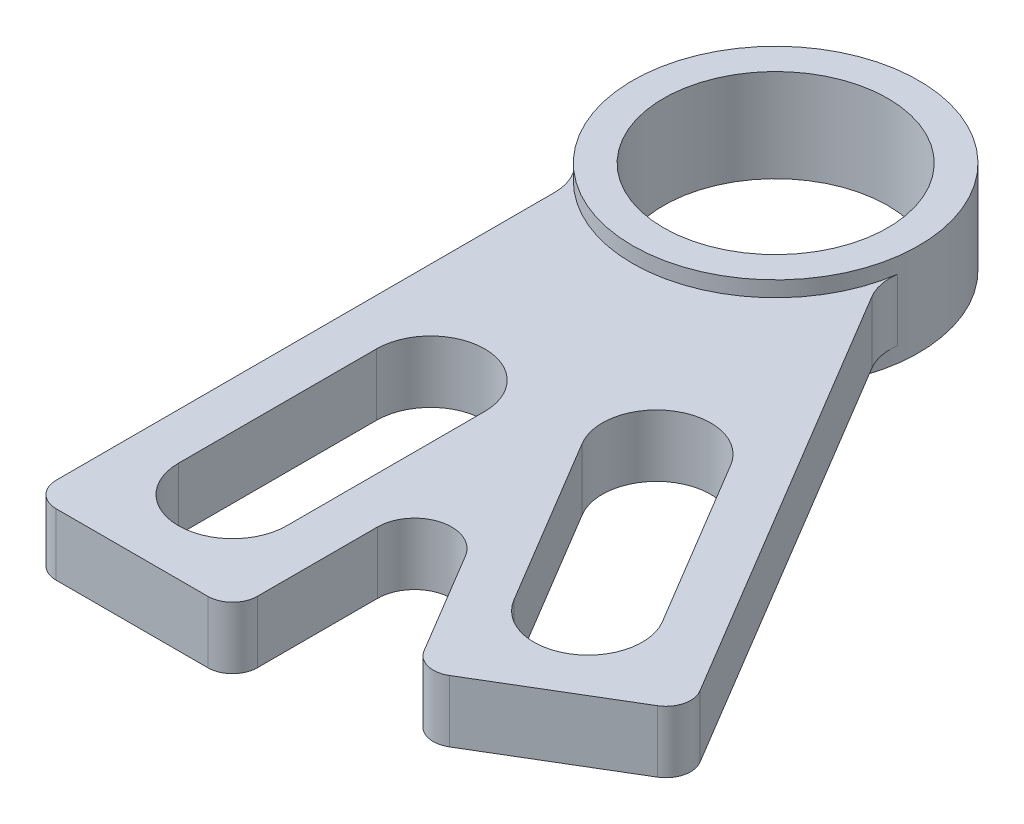
SolidWorks part; units mm, degrees
material "AISI 4130 Steel, normalized at 870C"
ref_plane "Front Plane" through (0, 0, 0) normal (0, 0, 1) x (1, 0, 0)
ref_plane "Top Plane" through (0, 0, 0) normal (0, 1, 0) x (1, 0, 0)
ref_plane "Right Plane" through (0, 0, 0) normal (1, 0, 0) x (0, 0, -1)
sketch "Sketch1" plane through (0, 0, 0) normal (0, 1, 0) x (1, 0, 0)
  line L0 (0, 0) -> (0, -66.04) construction
  line L1 (0, 0) -> (33.8815, -56.6862) construction
  line L2 (0, -55.7213) -> (0, -35.4013) construction
  line L3 (-5.5562, -55.7213) -> (-5.5562, -35.4013)
  line L4 (5.5563, -55.7213) -> (5.5563, -35.4013)
  line L5 (28.5875, -47.829) -> (18.1624, -30.3871) construction
  line L6 (23.8182, -50.6796) -> (13.3931, -33.2377)
  line L7 (33.3568, -44.9784) -> (22.9317, -27.5365)
  line L8 (0, -66.04) -> (0, -61.2775) construction
  line L9 (33.8815, -56.6862) -> (31.4381, -52.5983) construction
  line L10 (-10.3187, -66.04) -> (10.3188, -66.04)
  line L11 (25.0242, -61.9802) -> (42.7387, -51.3923)
  line L12 (-10.3187, -66.04) -> (-10.3187, -10.4432)
  line L13 (10.3188, -66.04) -> (10.3188, -37.3768)
  line L14 (42.7387, -51.3923) -> (14.2151, -3.6701)
  line L15 (25.0242, -61.9802) -> (10.3188, -37.3768)
  line L16 (189.0018, -316.2143) -> (17.7009, -29.6149) construction
  line L22 (0, 0) -> (10.3188, -37.3768) construction
  circle A0 centre (0, 0) radius 11.5062
  circle A1 centre (0, 0) radius 14.6812
  arc A2 (-5.5562, -55.7213) -> (5.5563, -55.7213) centre (0, -55.7213) ccw
  arc A3 (5.5563, -35.4013) -> (-5.5562, -35.4013) centre (0, -35.4013) ccw
  arc A4 (23.8182, -50.6796) -> (33.3568, -44.9784) centre (28.5875, -47.829) ccw
  arc A5 (22.9317, -27.5365) -> (13.3931, -33.2377) centre (18.1624, -30.3871) ccw
  point P8 (0, -45.5613)
  point P13 (23.3749, -39.108)
  point P25 (0, -66.04)
  point P27 (33.8815, -56.6862)
  dimension "D2" = 29.3624
  dimension "D3" = 4.7625
  dimension "D4" = 4.7625
  dimension "D5" = 20.32
  dimension "D6" = 66.04
  dimension "D7" = 20.6375
extrude "Bearing_Insert_Extrude" add sketch "Sketch1" along normal mid plane 9.525 contours A1 A0 region at (-5.4988, 0, -13.1636)
extrude "Apex_Slot_Insert_Extrude" add sketch "Sketch1<4>" along normal mid plane 6.35 contours A1 L12 L10 L13 L15 L11 L14 A5 L7 A4 L6 A3 L4 A2 L3 | L13 L15 region at (9.9891, 0, 36.1827)
sketch "Sketch1<4>" plane through (0, 0, 0) normal (0, 1, 0) x (1, 0, 0) same geometry as "Sketch1"
fillet "Fillet1" radius 5.08 2 edges at (14.2151, 0, 3.6701) (-10.3187, 0, 10.4432)
fillet "Fillet2" radius 2.54 4 edges at (42.7387, 0, 51.3923) (25.0242, 0, 61.9802) (10.3188, 0, 66.04) (-10.3187, 0, 66.04)
fillet "Fillet3" radius 3.81 1 edges at (10.3188, 0, 37.3768)
equation "\"Apex_thickness\"= .25"
equation "\"Bearing_diameter\"= 0.906in"
equation "\"A-arm_angle\"= 39.1893"
equation "\"D1@Sketch1\"=\"Bearing_diameter\""
equation "\"D1@Apex_Slot_Insert_Extrude\"=\"Apex_thickness\""
